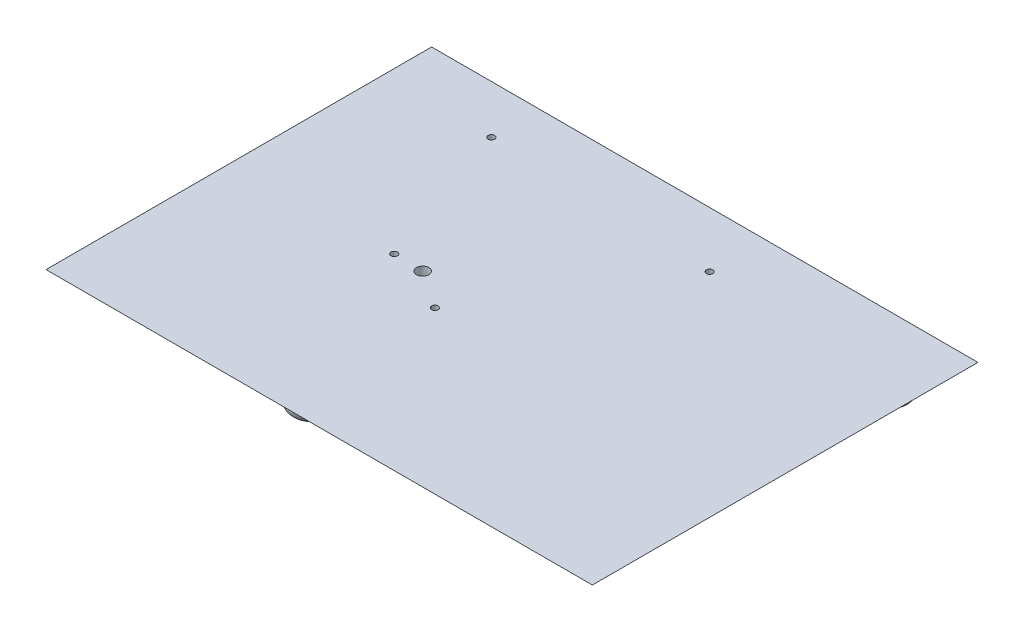
SolidWorks part; units mm, degrees
note: The reader was unsure of these and kept them because the rebuilt part matched: shared geometry of "Sketch1<5>", "Sketch1<6>", "Sketch1<7>", "Sketch1<9>", "Sketch1<10>", "Sketch1<11>".
ref_plane "Front Plane" through (0, 0, 0) normal (0, 0, 1) x (1, 0, 0)
ref_plane "Top Plane" through (0, 0, 0) normal (0, 1, 0) x (1, 0, 0)
ref_plane "Right Plane" through (0, 0, 0) normal (1, 0, 0) x (0, 0, -1)
sketch "Sketch1" plane through (0, 0, 0) normal (0, 1, 0) x (1, 0, 0)
  line L0 (30.7649, 4.1711) -> (30.7649, 6.6838)
  line L1 (-18.5365, 26.9521) -> (229.4635, 26.9521)
  line L2 (-18.5365, 26.9521) -> (-18.5365, -148.0479)
  line L3 (-18.5365, -148.0479) -> (229.4635, -148.0479)
  line L4 (229.4635, 26.9521) -> (229.4635, -148.0479)
  line L5 (-18.5365, -65.241) -> (52.1254, -65.241) construction
  line L6 (52.1254, -65.241) -> (52.1254, -148.0479) construction
  line L11 (65.9743, -65.5479) -> (65.9743, -148.0479) construction
  line L12 (65.9743, -65.5479) -> (-18.5365, -65.5479) construction
  line L13 (84.0135, -77.7455) -> (84.0135, -148.0479) construction
  line L14 (84.0135, -77.7455) -> (-18.5365, -77.7455) construction
  line L15 (27.1635, 5.9521) -> (-18.5365, 5.9521) construction
  line L16 (27.1635, 5.9521) -> (27.1635, 26.9521) construction
  line L18 (134.4738, 26.9521) -> (134.4738, 2.474) construction
  line L19 (134.4738, 2.474) -> (229.4635, 2.474) construction
  line L20 (-18.5365, 11.7521) -> (0.2435, 11.7521) construction
  line L21 (0.2435, 26.9521) -> (0.2435, 11.7521) construction
  line L22 (-18.5365, -130.9527) -> (78.4619, -130.9527) construction
  line L23 (78.4619, -130.9527) -> (78.4619, -148.0479) construction
  line L24 (229.4635, 11.7521) -> (210.6835, 11.7521) construction
  line L25 (210.6835, 11.7521) -> (210.6835, 26.9521) construction
  circle A0 centre (27.1635, 5.9521) radius 3.675
  circle A1 centre (27.1635, 5.9521) radius 1.56
  circle A4 centre (52.1254, -65.241) radius 1.5642
  circle A5 centre (52.1254, -65.241) radius 3.675
  circle A6 centre (65.9743, -65.5479) radius 5.43
  circle A7 centre (65.9743, -65.5479) radius 2.9469
  circle A10 centre (84.0135, -77.7455) radius 1.5638
  circle A11 centre (84.0135, -77.7455) radius 3.675
  circle A12 centre (134.4738, 2.474) radius 1.56
  circle A13 centre (134.4738, 2.474) radius 3.675
  circle A18 centre (0.2435, 11.7521) radius 9.9
  circle A19 centre (210.6835, 11.7521) radius 9.9
  circle A20 centre (78.4619, -130.9527) radius 9.9
  dimension "D3" = 7.35
  dimension "D4" = 3.12
  dimension "D6" = 7.35
  dimension "D7" = 10.86
  dimension "D8" = 21
  dimension "D9" = 7.35
  dimension "D15" = 7.35
  dimension "D16" = 3.12
  dimension "D17" = 18.78
  dimension "D21" = 19.8
  dimension "D22" = 19.8
  dimension "D19" = 19.8
  dimension "D1" = 248
  dimension "D2" = 175
  dimension "D5" = 45.7
  dimension "D10" = 70.6619
  dimension "D11" = 82.807
  dimension "D12" = 82.5
  dimension "D13" = 70.3024
  dimension "D14" = 102.55
  dimension "D18" = 15.2
ref_plane "Plane1" through (0, 0, 0) normal (0, 1, 0) x (1, 0, 0)
ref_plane "Plane2" through (0, 6, 0) normal (0, 1, 0) x (1, 0, 0)
sketch "Sketch3" plane through (0, 6, 0) normal (0, 1, 0) x (1, 0, 0)
  line L8 (235.7146, -154.5408) -> (-24.2854, -154.5408)
  line L9 (235.7146, -154.5408) -> (235.7146, 28.9592)
  line L10 (235.7146, 28.9592) -> (-24.2854, 28.9592)
  line L11 (-24.2854, -154.5408) -> (-24.2854, 28.9592)
  line L12 (235.7146, -154.5408) -> (-24.2854, 28.9592) construction
  line L13 (235.7146, 28.9592) -> (-24.2854, -154.5408) construction
  point P0 (105.7146, -62.7908)
  point P1 (105.7146, -62.7908)
  dimension "D1" = 260
  dimension "D2" = 183.5
loft "Loft2" add profiles "Sketch3" section "Sketch3" section "Sketch1" connector at (235.7146, 6, -28.9592) connector at (229.4635, 0, -26.9521)
extrude "Cut-Extrude1" cut sketch "Sketch1<5>" along normal blind 6 contours A4
sketch "Sketch1<5>" plane through (0, 0, 0) normal (0, 1, 0) x (1, 0, 0) same geometry as "Sketch1"
extrude "Cut-Extrude2" cut sketch "Sketch1<6>" along normal blind 6
sketch "Sketch1<6>" plane through (0, 0, 0) normal (0, 1, 0) x (1, 0, 0) same geometry as "Sketch1"
extrude "Boss-Extrude2" add sketch "Sketch1<7>" against normal blind 1
sketch "Sketch1<7>" plane through (0, 0, 0) normal (0, 1, 0) x (1, 0, 0) same geometry as "Sketch1"
ref_plane "Plane3" through (0, 83, 0) normal (0, 1, 0) x (1, 0, 0)
sketch "Sketch10" plane through (0, 83, 0) normal (0, 1, 0) x (1, 0, 0)
  line L0 (235.7146, 28.9592) -> (-24.2854, -154.5408) construction
  line L1 (-34.2797, 32.4154) -> (245.7088, 32.4154)
  line L2 (-34.2797, 32.4154) -> (-34.2797, -157.9969)
  line L3 (-34.2797, -157.9969) -> (245.7088, -157.9969)
  line L4 (245.7088, 32.4154) -> (245.7088, -157.9969)
  line L5 (-34.2797, 32.4154) -> (245.7088, -157.9969) construction
  line L6 (-34.2797, -157.9969) -> (245.7088, 32.4154) construction
  point P0 (105.7146, -62.7908)
  point P1 (105.7146, -62.7908)
extrude "Cut-Extrude9" cut sketch "Sketch1<9>" along normal blind 10 contours A12
sketch "Sketch1<9>" plane through (0, 0, 0) normal (0, 1, 0) x (1, 0, 0) same geometry as "Sketch1"
extrude "Cut-Extrude11" cut sketch "Sketch1<10>" along normal blind 10 contours A10
sketch "Sketch1<10>" plane through (0, 0, 0) normal (0, 1, 0) x (1, 0, 0) same geometry as "Sketch1"
extrude "Boss-Extrude3" add sketch "Sketch1<11>" against normal blind 12.5 contours A19 | A20 | A18
sketch "Sketch1<11>" plane through (0, 0, 0) normal (0, 1, 0) x (1, 0, 0) same geometry as "Sketch1"
fillet "Fillet1" radius 5 3 edges at (78.4619, -12.5, 140.8527) (210.6835, -12.5, -1.8521) (0.2435, -12.5, -1.8521)
